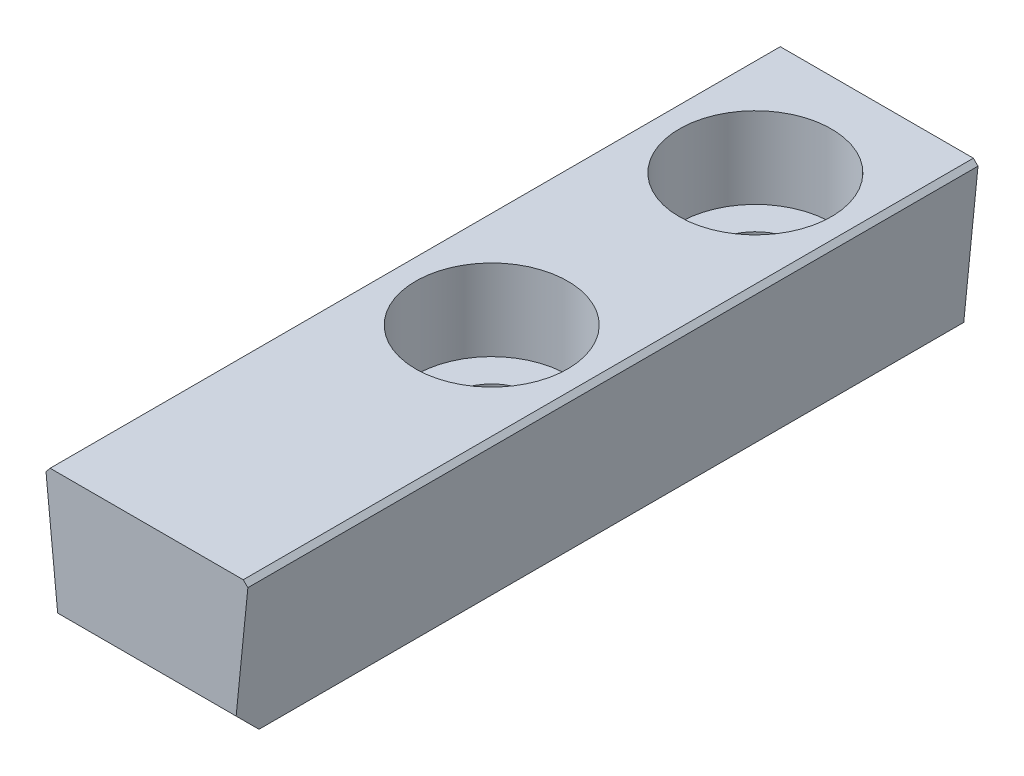
SolidWorks part; units mm, degrees
ref_plane "前视基准面" through (0, 0, 0) normal (0, 0, 1) x (1, 0, 0)
ref_plane "上视基准面" through (0, 0, 0) normal (0, 1, 0) x (1, 0, 0)
ref_plane "右视基准面" through (0, 0, 0) normal (1, 0, 0) x (0, 0, -1)
sketch "草图1" plane through (0, 0, 0) normal (0, 0, 1) x (1, 0, 0)
  line L0 (0, 0) -> (0, 33.4703) construction
  line L1 (0, -55) -> (0, 55) construction
  line L2 (-8.5, 0) -> (8.5, 0)
  line L3 (55, 0) -> (-55, 0) construction
  line L4 (8.5, 0) -> (10, 15)
  line L5 (10, 15) -> (-10, 15)
  line L6 (-8.5, 0) -> (-10, 15)
  point P11 (0, 15)
  dimension "D1" = 17
  dimension "D2" = 20
  dimension "D3" = 15
extrude "凸台-拉伸1" add sketch "草图1" against normal blind 72
chamfer "倒角1" distance 3 angle 45 1 edges at (0, 0, 0)
sketch "草图2" plane through (0, 0, 0) normal (0, -1, 0) x (1, 0, 0)
  line L0 (8.5, -22) -> (-8.5, -22)
  line L1 (8.5, -72) -> (8.5, -3) construction
  line L2 (-8.5, -72) -> (-8.5, -3) construction
  line L3 (-8.5, -72) -> (8.5, -72) construction
  dimension "D1" = 50
extrude "切除-拉伸-薄壁1" cut sketch "草图2" against normal blind 0.5 and the other way through all thin
sketch "草图3" plane through (0, 15, 0) normal (0, 1, 0) x (1, 0, 0)
  line L0 (0, 34) -> (0, 60) construction
  line L1 (10, 72) -> (-10, 72) construction
  point P0 (0, 34)
  point P1 (0, 60)
  dimension "D1" = 12
  dimension "D2" = 26
hole_wizard "孔1" positions "草图3" profile "草图4" legacy end condition through all
sketch "草图4" plane through (0, 15, -34) normal (1, 0, 0) x (0, 0, 1)
  line L0 (0, 0) -> (0, 15)
  line L1 (0, 15) -> (4.2, 15)
  line L2 (4.2, 15) -> (4.2, 8)
  line L3 (4.2, 8) -> (7.5, 8)
  line L4 (7.5, 8) -> (7.5, 0)
  line L5 (7.5, 0) -> (0, 0)
  line L6 (0, 110) -> (0, -10) construction
  dimension "直径" = 8.4
  dimension "深度" = 15
  dimension "柱坑直径" = 15
  dimension "柱坑深度" = 8
chamfer "倒角2" distance 0.5 angle 45 4 edges at (10, 15, -36) (-10, 15, -36) (-8.5, 0, -11.5) (8.5, 0, -47)
